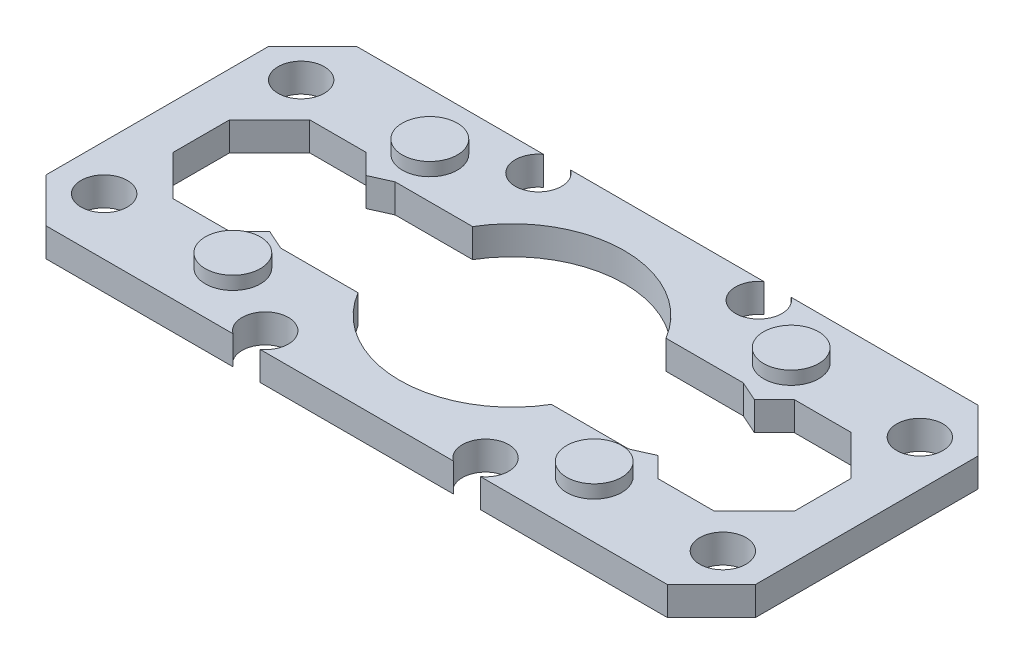
SolidWorks part; units mm, degrees
ref_plane "Front" through (0, 0, 0) normal (0, 0, 1) x (1, 0, 0)
ref_plane "Top" through (0, 0, 0) normal (0, 1, 0) x (1, 0, 0)
ref_plane "Right" through (0, 0, 0) normal (1, 0, 0) x (0, 0, -1)
sketch "Sketch1" plane through (0, 0, 0) normal (0, 1, 0) x (1, 0, 0)
  line L0 (-5.5671, 8.9535) -> (5.5671, 8.9535)
  line L1 (-6.35, -7.874) -> (6.35, -7.874) construction
  line L2 (-6.35, -7.874) -> (-6.35, 7.874) construction
  line L3 (-6.35, 7.874) -> (6.35, 7.874) construction
  line L4 (6.35, -7.874) -> (6.35, 7.874) construction
  line L5 (-6.35, -7.874) -> (6.35, 7.874) construction
  line L6 (-6.35, 7.874) -> (6.35, -7.874) construction
  line L7 (-17.8308, -5.6769) -> (17.8308, -5.6769) construction
  line L8 (-17.8308, -5.6769) -> (-17.8308, 5.6769) construction
  line L9 (-17.8308, 5.6769) -> (17.8308, 5.6769) construction
  line L10 (17.8308, -5.6769) -> (17.8308, 5.6769) construction
  line L11 (-17.8308, -5.6769) -> (17.8308, 5.6769) construction
  line L12 (-17.8308, 5.6769) -> (17.8308, -5.6769) construction
  line L13 (-10.414, -5.6769) -> (10.414, -5.6769) construction
  line L14 (-10.414, -5.6769) -> (-10.414, 5.6769) construction
  line L15 (-10.414, 5.6769) -> (10.414, 5.6769) construction
  line L16 (10.414, -5.6769) -> (10.414, 5.6769) construction
  line L17 (-10.414, -5.6769) -> (10.414, 5.6769) construction
  line L18 (-10.414, 5.6769) -> (10.414, -5.6769) construction
  line L19 (-20.447, -8.9535) -> (-7.1329, -8.9535)
  line L20 (-20.447, -8.9535) -> (-20.447, 8.9535)
  line L21 (-20.447, 8.9535) -> (-7.1329, 8.9535)
  line L22 (20.447, -8.9535) -> (20.447, 8.9535)
  line L23 (-20.447, -8.9535) -> (20.447, 8.9535) construction
  line L24 (-20.447, 8.9535) -> (20.447, -8.9535) construction
  line L25 (7.1329, 8.9535) -> (20.447, 8.9535)
  line L26 (7.1329, -8.9535) -> (20.447, -8.9535)
  line L27 (-5.5671, -8.9535) -> (5.5671, -8.9535)
  circle A0 centre (-17.8308, 5.6769) radius 1.3335
  arc A1 (-7.1329, 8.9535) -> (-5.5671, 8.9535) centre (-6.35, 7.874) ccw
  arc A2 (5.5671, 8.9535) -> (7.1329, 8.9535) centre (6.35, 7.874) ccw
  circle A3 centre (17.8308, 5.6769) radius 1.3335
  circle A4 centre (17.8308, -5.6769) radius 1.3335
  arc A5 (7.1329, -8.9535) -> (5.5671, -8.9535) centre (6.35, -7.874) ccw
  arc A6 (-5.5671, -8.9535) -> (-7.1329, -8.9535) centre (-6.35, -7.874) ccw
  circle A7 centre (-17.8308, -5.6769) radius 1.3335
  circle A8 centre (-10.414, 5.6769) radius 1.5875
  circle A9 centre (10.414, 5.6769) radius 1.5875
  circle A10 centre (10.414, -5.6769) radius 1.5875
  circle A11 centre (-10.414, -5.6769) radius 1.5875
  point P0 (0, 0)
  point P6 (0, 0)
  point P11 (0, 0)
  point P16 (0, 0)
  dimension "D8" = 2.667
  dimension "D9" = 3.175
  dimension "D1" = 12.7
  dimension "D2" = 15.748
  dimension "D3" = 11.3538
  dimension "D4" = 35.6616
  dimension "D5" = 40.894
  dimension "D6" = 17.907
  dimension "D7" = 20.828
extrude "Boss-Extrude1" add sketch "Sketch1" along normal blind 1.651
chamfer "Chamfer1" distance 2.54 angle 45 4 edges at (-20.447, 0.8255, 8.9535) (-20.447, 0.8255, -8.9535) (20.447, 0.8255, -8.9535) (20.447, 0.8255, 8.9535)
extrude "Boss-Extrude2" add sketch "Sketch1<2>" along normal blind 2.413 contours A8 | A9 | A10 | A11
sketch "Sketch1<2>" plane through (0, 0, 0) normal (0, 1, 0) x (1, 0, 0) same geometry as "Sketch1"
extrude "Cut-Extrude1" cut sketch "Sketch1<3>" along normal blind 0.889 contours A11 | A10 | A9 | A8
sketch "Sketch1<3>" plane through (0, 0, 0) normal (0, 1, 0) x (1, 0, 0) same geometry as "Sketch1"
sketch "Sketch2" plane through (0, 1.651, 0) normal (0, 1, 0) x (1, 0, 0)
  line L1 (-17.907, -3.937) -> (17.907, -3.937) construction
  line L2 (-17.907, -3.937) -> (-17.907, 3.937) construction
  line L3 (-17.907, 3.937) -> (17.907, 3.937) construction
  line L4 (17.907, -3.937) -> (17.907, 3.937) construction
  line L5 (-17.907, -3.937) -> (17.907, 3.937) construction
  line L6 (-17.907, 3.937) -> (17.907, -3.937) construction
  line L7 (-17.907, 1.6308) -> (-17.907, -1.6308)
  line L8 (-17.907, -1.6308) -> (-15.6008, -3.937)
  line L9 (-15.6008, -3.937) -> (-12.3392, -3.937)
  line L10 (-12.3392, -3.937) -> (-11.1861, -2.7839)
  line L13 (-12.3392, 3.937) -> (-15.6008, 3.937)
  line L14 (-15.6008, 3.937) -> (-17.907, 1.6308)
  line L15 (17.907, 1.6308) -> (15.6008, 3.937)
  line L16 (15.6008, 3.937) -> (12.3392, 3.937)
  line L17 (12.3392, 3.937) -> (11.1861, 2.7839)
  line L20 (12.3392, -3.937) -> (15.6008, -3.937)
  line L21 (15.6008, -3.937) -> (17.907, -1.6308)
  line L22 (17.907, -1.6308) -> (17.907, 1.6308)
  line L23 (-10.033, -3.302) -> (-5.5721, -3.302)
  line L25 (-10.033, 3.302) -> (-5.5721, 3.302)
  line L27 (-10.033, -3.302) -> (10.033, 3.302) construction
  line L28 (-10.033, 3.302) -> (10.033, -3.302) construction
  line L30 (5.5721, 3.302) -> (10.033, 3.302)
  line L31 (5.5721, -3.302) -> (10.033, -3.302)
  line L32 (-11.1861, 2.7839) -> (-10.033, 3.302)
  line L33 (-11.1861, -2.7839) -> (-10.033, -3.302)
  line L34 (10.033, -3.302) -> (11.1861, -2.7839)
  line L35 (10.033, 3.302) -> (11.1861, 2.7839)
  line L36 (-11.1861, 2.7839) -> (-12.3392, 3.937)
  line L37 (-10.033, 1.6308) -> (-10.7701, 2.3679) [skipped]
  line L38 (11.1861, -2.7839) -> (12.3392, -3.937)
  line L39 (-10.033, -1.6308) -> (-10.033, -2.2058) [skipped]
  line L40 (10.033, -1.6308) -> (10.7701, -2.3679) [skipped]
  line L42 (10.033, 2.2058) -> (10.033, 3.302) [skipped]
  arc A0 (-5.5721, -3.302) -> (5.5721, -3.302) centre (0, 0) ccw
  circle A1 centre (-13.97, 0) radius 3.937 construction
  circle A2 centre (13.97, 0) radius 3.937 construction
  arc A4 (5.5721, 3.302) -> (-5.5721, 3.302) centre (0, 0) ccw
  point P13 (0, 0)
  point P14 (-11.1861, 2.7839)
  dimension "D1" = 12.954
  dimension "D2" = 35.814
  dimension "D3" = 7.874
  dimension "D4" = 6.604
  dimension "D5" = 20.066
  dimension "D6" = 11.1442
  dimension "D8" = 5.5678
extrude "Cut-Extrude2" cut sketch "Sketch2" against normal through all
